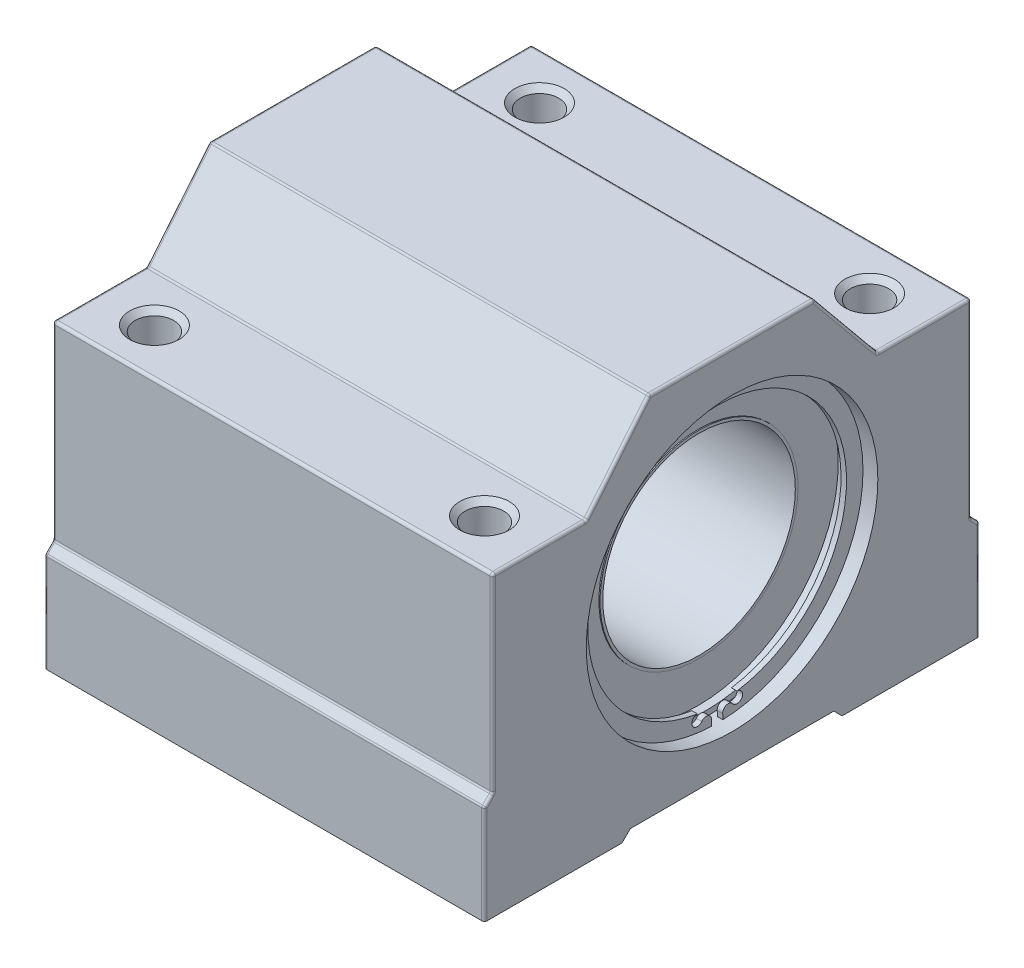
SolidWorks part; units mm, degrees
ref_plane "Front Plane" through (0, 0, 0) normal (0, 0, 1) x (1, 0, 0)
ref_plane "Top Plane" through (0, 0, 0) normal (0, 1, 0) x (1, 0, 0)
ref_plane "Right Plane" through (0, 0, 0) normal (1, 0, 0) x (0, 0, -1)
sketch "Sketch1" plane through (0, 0, 0) normal (1, 0, 0) x (0, 0, -1)
  line L1 (-20, -34) -> (-18.5, -32.5)
  line L2 (-18.5, -32.5) -> (18.5, -32.5)
  line L3 (18.5, -32.5) -> (20, -34)
  line L4 (20, -34) -> (45, -34)
  line L6 (45, -16) -> (43.5, -14.5)
  line L8 (43.5, 20) -> (26.5, 20)
  line L9 (26.5, 20) -> (15, 34)
  line L10 (15, 34) -> (-15, 34)
  line L11 (-15, 34) -> (-26.5, 20)
  line L12 (-26.5, 20) -> (-43.5, 20)
  line L15 (-45, -16) -> (-45, -34)
  line L16 (0, -32.5) -> (0, 34) construction
  line L17 (-16.278, 0) -> (14.0247, 0) construction
  line L18 (-45, -34) -> (-20, -34)
  line L19 (45, -16) -> (45, -34)
  line L20 (-43.5, -14.5) -> (-43.5, 20)
  line L21 (43.5, -14.5) -> (43.5, 20)
  line L22 (-35, 20) -> (-35, -34) construction
  line L23 (-35, -34) -> (35, 20) construction
  line L24 (35, 20) -> (35, -34) construction
  line L25 (-45, -16) -> (-43.5, -14.5)
  line L26 (-26.5, 0) -> (26.5, 0) construction
  circle A0 centre (0, 0) radius 26.5
  circle A1 centre (0, 0) radius 25.5
  circle A2 centre (0, 0) radius 17.5
  point P18 (0, 34)
  dimension "D12" = 35
  dimension "D1" = 90
  dimension "D2" = 54
  dimension "D3" = 34
  dimension "D5" = 68
  dimension "D6" = 70
  dimension "D4" = 18
  dimension "D7" = 1.5
  dimension "D8" = 30
  dimension "D9" = 1.5
  dimension "D10" = 25
  dimension "D11" = 1
extrude "Boss-Extrude1" add sketch "Sketch1" along normal blind 80 contours L25 L15 L18 L1 L2 L3 L4 L19 L6 L21 L8 L9 L10 L11 L12 L20 A0 region at (0, -32.872, 32.5)
extrude "Extrude-Thin1" add sketch "Sketch1<4>" along normal blind 73.5 from offset 0.5 separate body thin contours A2 thin type one direction wall 0.5
sketch "Sketch1<4>" plane through (0, 0, 0) normal (1, 0, 0) x (0, 0, -1) same geometry as "Sketch1"
extrude "Boss-Extrude2" add sketch "Sketch1<5>" along normal blind 73 from offset 0.8 contours A1 A2 region at (0, 0, 24.7788)
sketch "Sketch1<5>" plane through (0, 0, 0) normal (1, 0, 0) x (0, 0, -1) same geometry as "Sketch1"
extrude "Boss-Extrude3" add sketch "Sketch1<6>" along normal blind 75 from offset 0.3 contours A0 A1 region at (0, 0, 25.7505)
sketch "Sketch1<6>" plane through (0, 0, 0) normal (1, 0, 0) x (0, 0, -1) same geometry as "Sketch1"
ref_plane "Plane1" through (75.3, 0, 0) normal (1, 0, 0) x (0, 0, -1)
sketch "Sketch3" plane through (75.3, 0, 0) normal (1, 0, 0) x (0, 0, -1)
  line L0 (0, 0) -> (0, -50000) construction
  line L1 (-1.0017, -25.4803) -> (-1.041, -26.4795)
  line L2 (1.0017, -25.4803) -> (1.041, -26.4795)
  circle A0 centre (0, 0) radius 26.5 construction
  arc A1 (1.041, -26.4795) -> (-1.041, -26.4795) centre (0, 0) ccw
  circle A2 centre (0, 0) radius 25.5 construction
  arc A3 (0, -25.5) -> (1.0017, -25.4803) centre (0, 0) ccw
  arc A4 (-1.0017, -25.4803) -> (-2.8042, -24.8271) centre (-2, -25.4214) ccw
  circle A5 centre (-2, -25.4214) radius 0.25
  arc A6 (-2.2491, -25.4006) -> (-1.7507, -25.4398) centre (0, 0) ccw
  arc A7 (-2.8042, -24.8271) -> (-3.6006, -23.2328) centre (-3.6085, -24.2328) cw
  arc A8 (2.8042, -24.8271) -> (3.6006, -23.2328) centre (3.6085, -24.2328) ccw
  circle A10 centre (2, -25.4214) radius 0.25
  arc A11 (1.0017, -25.4803) -> (2.8042, -24.8271) centre (2, -25.4214) cw
  arc A13 (3.6006, -23.2328) -> (-3.6006, -23.2328) centre (0, 0) ccw
  dimension "D1" = 0.5
  dimension "D2" = 2
  dimension "D3" = 1
  dimension "D4" = 2
extrude "Boss-Extrude4" add sketch "Sketch3" along normal blind 1 from offset 1 contours A11 A8 A13 A7 A4 L1 A1 L2
fillet "Fillet1" radius 0.5 32 edges at (40, -14.5, -43.5) (40, -14.5, 43.5) (40, -16, 45) (40, -16, -45) (40, 20, -26.5) (40, 20, 26.5) (40, 34, 15) (40, 34, -15) (40, 20, -43.5) (40, 20, 43.5) (80, 27, -20.75) (80, 27, 20.75) (80, 2.75, 43.5) (0, -15.25, 44.25) (0, 27, 20.75) (80, -15.25, -44.25) (80, -25, -45) (80, 2.75, -43.5) (80, 34, 0) (80, 20, -35) (80, 20, 35) (80, -15.25, 44.25) (80, -25, 45) (0, -25, -45) (0, -15.25, -44.25) (0, 2.75, -43.5) (0, 27, -20.75) (0, 20, -35) (0, 34, 0) (0, -25, 45) (0, 2.75, 43.5) (0, 20, 35)
sketch "Sketch4" plane through (0, -34, 0) normal (0, -1, 0) x (1, 0, 0)
  line L0 (40, 45) -> (40, -45) construction
  line L1 (79.5, 45) -> (0.5, 45) construction
  line L2 (79.5, -45) -> (0.5, -45) construction
  line L4 (-4.9444, 35) -> (27.0918, 35) construction
  line L6 (0, 0) -> (36.1646, 0) construction
  circle A0 centre (10, 35) radius 3.5
  circle A1 centre (70, 35) radius 3.5
  circle A2 centre (70, -35) radius 3.5
  circle A3 centre (10, -35) radius 3.5
  dimension "D2" = 7
  dimension "D1" = 35
  dimension "D3" = 60
extrude "Cut-Extrude3" cut sketch "Sketch4" against normal through all
chamfer "Chamfer1" distance 1 angle 45 6 edges at (70, 20, -38.5) (10, 20, -38.5) (10, 20, 31.5) (70, 20, 31.5) (70, -34, 38.5) (10, -34, 31.5)
equation "\"D1@Boss-Extrude2\"= \"D1@Boss-Extrude1\" - 2 - 5"
equation "\"D1@Boss-Extrude3\"= \"D1@Boss-Extrude1\" - 5"
equation "\"D1@Sketch4\"= \"D6@Sketch1\" / 2"
equation "\"D1@Extrude-Thin1\"= \"D1@Boss-Extrude3\" - 1.5"
